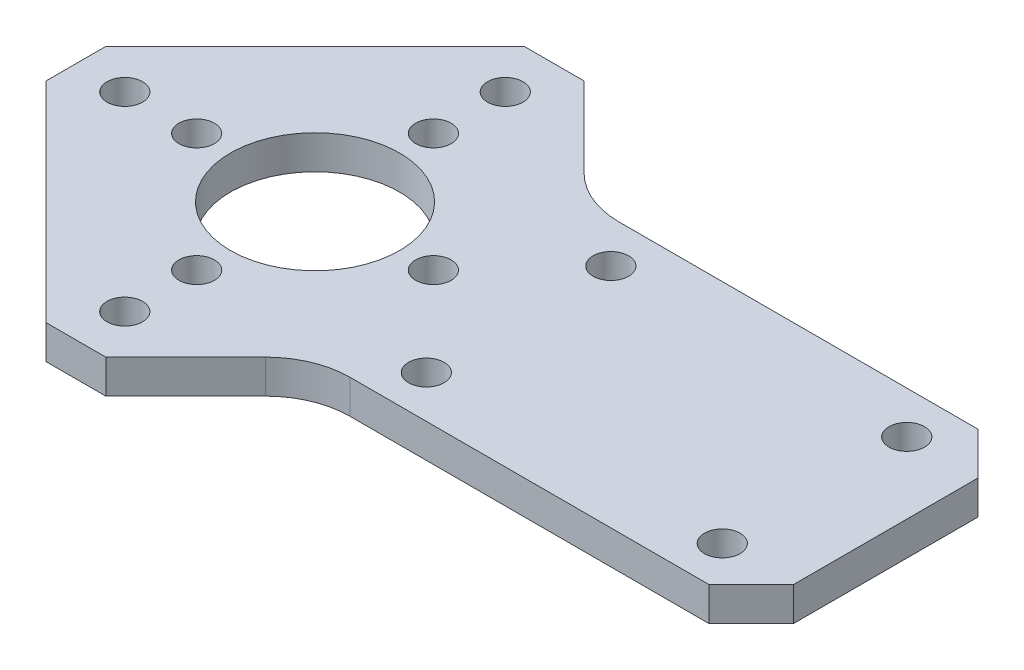
SolidWorks part; units mm, degrees
ref_plane "前视基准面" through (0, 0, 0) normal (0, 0, 1) x (1, 0, 0)
ref_plane "上视基准面" through (0, 0, 0) normal (0, 1, 0) x (1, 0, 0)
ref_plane "右视基准面" through (0, 0, 0) normal (1, 0, 0) x (0, 0, -1)
sketch "草图1" plane through (0, 0, 0) normal (0, 1, 0) x (1, 0, 0)
  line L0 (0, 0) -> (-31.8198, 0) construction
  line L1 (0, 31.8198) -> (-31.8198, 0)
  line L2 (-31.8198, 0) -> (0, -31.8198)
  line L3 (0, -31.8198) -> (15.9099, -15.9099)
  line L4 (15.9099, 15.9099) -> (0, 31.8198)
  line L5 (0, 0) -> (90, 0) construction
  line L6 (0, 0) -> (45, 77.9423) construction
  line L7 (45, 77.9423) -> (90, 0) construction
  line L8 (15.9099, 15.9099) -> (67.5, 15.9099)
  line L9 (15.9099, -15.9099) -> (67.5, -15.9099)
  line L10 (90, 0) -> (67.5, -22.5) construction
  line L11 (67.5, 22.5) -> (67.5, 15.9099)
  line L12 (67.5, -22.5) -> (112.5, -22.5)
  line L13 (112.5, -22.5) -> (112.5, 22.5)
  line L14 (112.5, 22.5) -> (67.5, 22.5)
  line L15 (67.5, -15.9099) -> (67.5, -22.5)
  line L16 (0, 0) -> (15.9099, 15.9099) construction
  line L17 (0, 0) -> (15.9099, -15.9099) construction
  circle A0 centre (0, 14) radius 2.1
  circle A1 centre (14, 0) radius 2.1
  circle A2 centre (0, -14) radius 2.1
  circle A3 centre (-14, 0) radius 2.1
  circle A4 centre (0, 0) radius 22.5 construction
  arc A5 (45, -77.9423) -> (45, 77.9423) centre (0, 0) ccw construction
  arc A6 (45, 77.9423) -> (45, -77.9423) centre (90, 0) ccw construction
  circle A7 centre (90, 0) radius 10.5
  circle A8 centre (90, 0) radius 22.5 construction
  circle A9 centre (0, 22.5) radius 2.1
  circle A11 centre (0, -22.5) radius 2.1
  circle A12 centre (0, 0) radius 10
  circle A13 centre (0, 0) radius 14 construction
  circle A14 centre (-22.5, 0) radius 2.1
  dimension "D1" = 4.2
  dimension "D2" = 20
  dimension "D3" = 4.2
  dimension "D4" = 4.2
  dimension "D5" = 4.2
  dimension "D6" = 45
  dimension "D9" = 180
  dimension "D10" = 180
  dimension "D11" = 21
  dimension "D14" = 4.2
  dimension "D15" = 4.2
  dimension "D17" = 4.2
  dimension "D7" = 180
  dimension "D8" = 90
  dimension "D12" = 135
  dimension "D13" = 45
extrude "凸台-拉伸1" add sketch "草图1" along normal blind 4
chamfer "倒角1" distance 5 angle 45 5 edges at (112.5, 2, 22.5) (112.5, 2, -22.5) (0, 2, 31.8198) (-31.8198, 2, 0) (0, 2, -31.8198)
fillet "圆角1" radius 10 4 edges at (15.9099, 2, -15.9099) (15.9099, 2, 15.9099) (67.5, 2, 15.9099) (67.5, 2, -15.9099)
sketch "草图2" plane through (0, 0, 0) normal (0, -1, 0) x (1, 0, 0)
  line L0 (39.0757, 15.9099) -> (39.0757, 10.9099) construction
  line L1 (20.052, 15.9099) -> (58.0993, 15.9099) construction
  line L2 (39.0757, 10.9099) -> (24.0757, 10.9099) construction
  line L3 (39.0757, 10.9099) -> (59.0757, 10.9099) construction
  line L4 (110, 20) -> (90, 0) construction
  line L5 (112.5, 17.5) -> (107.5, 22.5) construction
  line L6 (110, -20) -> (90, 0) construction
  line L7 (107.5, -22.5) -> (112.5, -17.5) construction
  line L8 (90, 22.5) -> (90, -22.5) construction
  line L9 (67.5, 22.5) -> (107.5, 22.5) construction
  line L10 (107.5, -22.5) -> (67.5, -22.5) construction
  line L11 (70, -20) -> (90, 0) construction
  line L12 (70, 20) -> (90, 0) construction
  line L13 (0, 0) -> (90, 0) construction
  line L14 (39.0757, -10.9099) -> (59.0757, -10.9099) construction
  line L15 (39.0757, -10.9099) -> (24.0757, -10.9099) construction
  line L16 (39.0757, -15.9099) -> (39.0757, -10.9099) construction
  circle A0 centre (106.4645, 16.4645) radius 2.1
  circle A1 centre (106.4645, -16.4645) radius 2.1
  circle A2 centre (73.5355, -16.4645) radius 2.1
  circle A3 centre (73.5355, 16.4645) radius 2.1
  circle A4 centre (24.0757, 10.9099) radius 2.1
  circle A5 centre (59.0757, 10.9099) radius 2.1
  circle A6 centre (59.0757, -10.9099) radius 2.1
  circle A7 centre (24.0757, -10.9099) radius 2.1
  dimension "D3" = 4.2
  dimension "D4" = 4.2
  dimension "D5" = 20
  dimension "D6" = 15
  dimension "D8" = 4.2
  dimension "D9" = 4.2
  dimension "D1" = 5
  dimension "D2" = 5
  dimension "D7" = 5
extrude "切除-拉伸1" cut sketch "草图2" against normal blind 10
sketch "草图3" plane through (0, 4, 0) normal (0, 1, 0) x (1, 0, 0)
  line L0 (0, 0) -> (90, 0) construction
  line L1 (45, 0) -> (45, 77.9423) construction
  line L2 (3.5355, 28.2843) -> (40.0576, 81.3442)
  line L3 (67.5, 22.5) -> (50.7578, 79.6297)
  line L4 (12.981, 18.8388) -> (3.5355, 28.2843) construction
  line L5 (58.0993, 15.9099) -> (20.052, 15.9099) construction
  line L6 (12.981, 18.8388) -> (3.5355, 28.2843)
  line L7 (58.0993, 15.9099) -> (20.052, 15.9099)
  line L8 (16.4918, 29.4702) -> (43.5266, 68.7468)
  line L9 (56.0801, 25.9099) -> (43.5266, 68.7468)
  line L10 (56.0801, 25.9099) -> (20.052, 25.9099)
  line L11 (20.052, 25.9099) -> (16.4918, 29.4702)
  circle A0 centre (45, 77.9423) radius 1.6
  arc A1 (50.7578, 79.6297) -> (40.0576, 81.3442) centre (45, 77.9423) ccw
  arc A2 (12.981, 18.8388) -> (20.052, 15.9099) centre (20.052, 25.9099) ccw construction
  arc A3 (58.0993, 15.9099) -> (67.5, 22.5) centre (58.0993, 25.9099) ccw construction
  arc A4 (12.981, 18.8388) -> (20.052, 15.9099) centre (20.052, 25.9099) ccw
  arc A5 (58.0993, 15.9099) -> (67.5, 22.5) centre (58.0993, 25.9099) ccw
  arc A6 (43.5266, 68.7468) -> (43.5266, 68.7468) centre (43.5266, 68.7468) ccw
  arc A7 (56.0801, 25.9099) -> (56.0801, 25.9099) centre (56.0801, 25.9099) ccw
  arc A8 (20.052, 25.9099) -> (20.052, 25.9099) centre (20.052, 25.9099) ccw
  dimension "D1" = 3.2
  dimension "D2" = 12
  dimension "D3" = 10
extrude "凸台-拉伸2" add sketch "草图3" against normal blind 3
fillet "圆角2" radius 3 4 edges at (20.052, 2.5, -25.9099) (16.4918, 2.5, -29.4702) (56.0801, 2.5, -25.9099) (43.5266, 2.5, -68.7468)
fillet "圆角3" radius 11 2 edges at (3.5355, 2.5, -28.2843) (67.5, 2.5, -22.5)
sketch "草图4" plane through (0, 4, 0) normal (0, 1, 0) x (1, 0, 0)
  line L0 (45.9493, 83.8667) -> (81.3477, 83.8667)
  line L3 (81.3477, 83.8667) -> (107.5, 22.5)
  line L4 (52.1537, 74.8667) -> (75.4, 74.8667)
  line L5 (75.4, 74.8667) -> (97.7168, 22.5)
  line L6 (107.5, 22.5) -> (75.739, 22.5) construction
  line L7 (73.0682, 80.3383) -> (99.2205, 18.9716) construction
  line L8 (45.9493, 74.8667) -> (90, 74.8667) construction
  line L9 (107.5, 22.5) -> (97.7168, 22.5)
  line L10 (65.183, 30.4065) -> (50.7578, 79.6297) construction
  line L11 (52.1537, 74.8667) -> (50.7578, 79.6297)
  line L12 (45.9493, 83.8667) -> (90, 83.8667) construction
  arc A0 (50.7578, 79.6297) -> (40.0576, 81.3442) centre (45, 77.9423) ccw construction
  circle A2 centre (78, 77.9423) radius 1.6
  arc A3 (50.7578, 79.6297) -> (45.9493, 83.8667) centre (45, 77.9423) ccw
  dimension "D1" = 33
extrude "凸台-拉伸3" add sketch "草图4" against normal blind 3
fillet "圆角4" radius 10 3 edges at (75.4, 2.5, -74.8667) (97.7168, 2.5, -22.5) (52.1537, 2.5, -74.8667)
chamfer "倒角2" distance 2 angle 32 1 edges at (81.3477, 2.5, -83.8667) first distance on face at (63.6485, 2.5, -83.8667)
fillet "圆角5" radius 10 1 edges at (107.5, 2.5, -22.5)
sketch "草图5" plane through (0, 4, 0) normal (0, 1, 0) x (1, 0, 0)
  line L0 (0, 0) -> (112.5, 0) construction
  line L1 (112.5, -17.5) -> (112.5, 17.5) construction
  line L2 (-3.5355, -28.2843) -> (3.5355, -28.2843) construction
  line L5 (67.5, -22.5) -> (67.5, -34.5529)
  line L8 (20.052, 15.9099) -> (58.0993, 15.9099)
  line L9 (3.5355, 28.2843) -> (12.981, 18.8388)
  line L10 (-3.5355, 28.2843) -> (3.5355, 28.2843)
  line L11 (67.5, 22.5) -> (67.5, -22.5)
  line L12 (-15.8142, 52.5248) -> (-3.5355, 28.2843)
  line L13 (-15.8142, 52.5248) -> (50.2644, 107.3572)
  line L14 (50.2644, 107.3572) -> (130.5194, 71.5353)
  line L15 (130.5194, 71.5353) -> (139.4749, -46.2639)
  line L16 (139.4749, -46.2639) -> (67.5, -34.5529)
  arc A0 (20.052, -15.9099) -> (12.981, -18.8388) centre (20.052, -25.9099) ccw construction
  arc A1 (67.5, -22.5) -> (58.0993, -15.9099) centre (58.0993, -25.9099) ccw construction
  arc A4 (67.5, 22.5) -> (58.0993, 15.9099) centre (58.0993, 25.9099) cw
  arc A5 (20.052, 15.9099) -> (12.981, 18.8388) centre (20.052, 25.9099) cw
extrude "切除-拉伸2" cut sketch "草图5" against normal blind 10
sketch "草图6" plane through (0, 4, 0) normal (0, 1, 0) x (1, 0, 0)
  line L0 (58.0993, 15.9099) -> (80.0445, 15.9099)
  line L1 (80.0445, 15.9099) -> (76.3886, 31.9889)
  line L2 (76.3886, 31.9889) -> (52.2931, 28.8316)
  line L3 (52.2931, 28.8316) -> (58.0993, 15.9099)
  line L4 (58.0993, -15.9099) -> (78.2165, -15.9099)
  line L5 (78.2165, -15.9099) -> (69.0719, -30.3271)
  line L6 (69.0719, -30.3271) -> (59.7992, -28.452)
  line L7 (59.7992, -28.452) -> (58.0993, -15.9099)
extrude "切除-拉伸3" cut sketch "草图6" against normal blind 10
chamfer "倒角3" distance 5 angle 45 2 edges at (67.5, 2, 15.9099) (67.5, 2, -15.9099)
